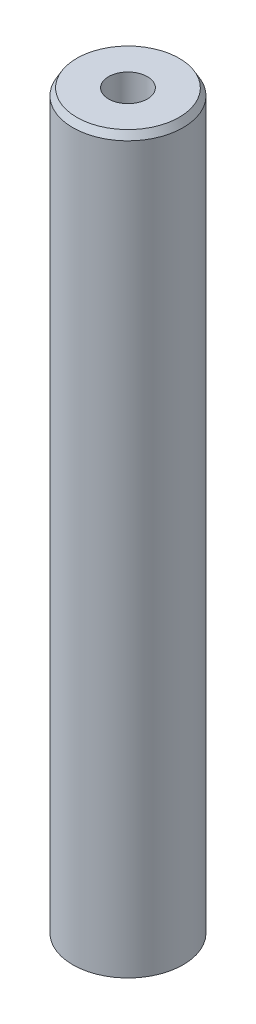
SolidWorks part; units mm, degrees
ref_plane "Front Plane" through (0, 0, 0) normal (0, 0, 1) x (1, 0, 0)
ref_plane "Top Plane" through (0, 0, 0) normal (0, 1, 0) x (1, 0, 0)
ref_plane "Right Plane" through (0, 0, 0) normal (1, 0, 0) x (0, 0, -1)
sketch "Sketch1" plane through (0, 0, 0) normal (0, 1, 0) x (1, 0, 0)
  circle A0 centre (0, 0) radius 45
  dimension "SHAFT_OD" = 90
extrude "Boss-Extrude1" add sketch "Sketch1" along normal blind 600
sketch "Sketch2" plane through (0, 0, 0) normal (0, 1, 0) x (1, 0, 0)
  circle A0 centre (0, 0) radius 15.8198
  dimension "BORE_D" = 31.6397
extrude "Cut-Extrude1" cut sketch "Sketch2" along normal through all
chamfer "Chamfer1" distance 5.6395 angle 30 2 edges at (0, 600, 45) (0, 0, 45) first distance on face at (0, 600, 45) first distance on face at (0, 0, 15.8198)
